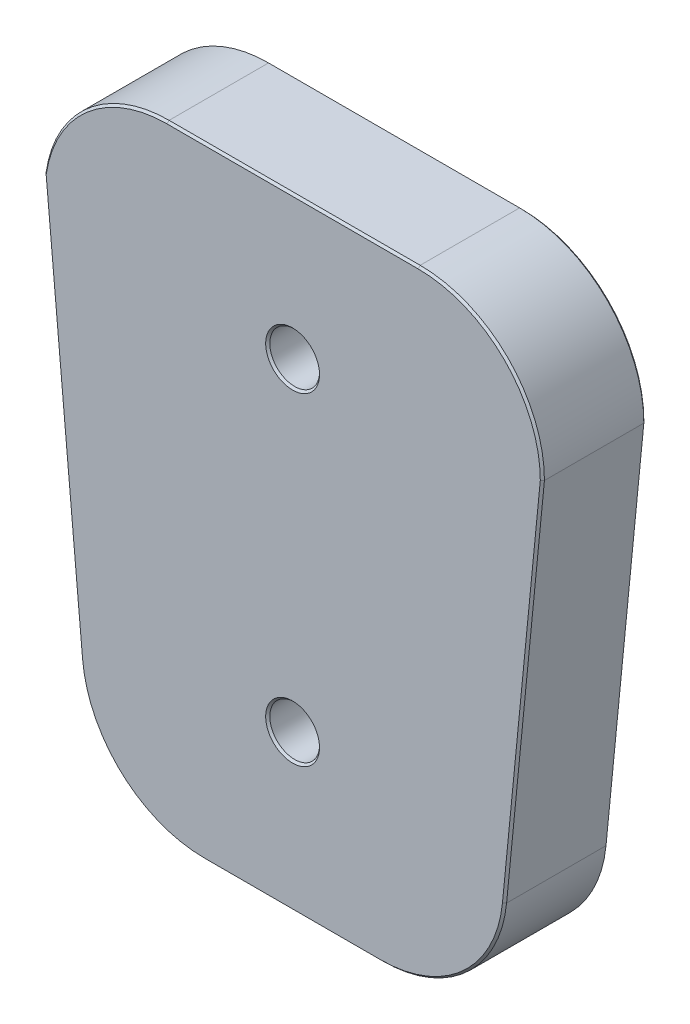
SolidWorks part; units mm, degrees
ref_plane "Front Plane" through (0, 0, 0) normal (0, 0, 1) x (1, 0, 0)
ref_plane "Top Plane" through (0, 0, 0) normal (0, 1, 0) x (1, 0, 0)
ref_plane "Right Plane" through (0, 0, 0) normal (1, 0, 0) x (0, 0, -1)
sketch "Sketch3" plane through (0, 0, 0) normal (0, 0, 1) x (1, 0, 0)
  line L0 (0, -25.6956) -> (8.8067, -122.7121)
  line L1 (29.6896, 0) -> (90.3104, 0)
  line L5 (38.6838, -150) -> (81.3162, -150)
  line L6 (111.1722, -122.9357) -> (120.3104, -30)
  line L7 (60, 0) -> (60, -173.3588) construction
  arc A0 (90.3104, 0) -> (120.3104, -30) centre (90.3104, -30) cw
  arc A1 (29.6896, 0) -> (0, -25.6956) centre (29.6896, -30) ccw
  arc A2 (81.3162, -150) -> (111.1722, -122.9357) centre (81.3162, -120) ccw
  arc A3 (8.8067, -122.7121) -> (38.6838, -150) centre (38.6838, -120) ccw
  point P7 (120, 0)
  point P10 (0, 0)
  point P13 (60, -150)
  dimension "D3" = 30
  dimension "D5" = 30
  dimension "D2" = 150
  dimension "D4" = 0
extrude "Boss-Extrude1" add sketch "Sketch3" along normal blind 25 contours A3 L5 A2 L6 A0 L1 A1 L0
sketch "Sketch4" plane through (0, 0, 25) normal (0, 0, 1) x (1, 0, 0)
  line L0 (60, 0) -> (60, -69) construction
  line L1 (29.6896, 0) -> (90.3104, 0) construction
  line L2 (38.6838, -150) -> (81.3162, -150) construction
  line L3 (60, 0) -> (60, -69) construction
  line L4 (60, -75) -> (60, -150) construction
  line L5 (60, -75) -> (60, -150) construction
  circle A1 centre (60, -34.5) radius 6
  circle A2 centre (60, -112.5) radius 6
  dimension "D1" = 12
  dimension "D3" = 12
extrude "Cut-Extrude1" cut sketch "Sketch4" against normal blind 12
sketch "Sketch5" plane through (0, 0, 13) normal (0, 0, 1) x (1, 0, 0)
  circle A0 centre (60, -34.5) radius 3.2
  circle A2 centre (60, -112.5) radius 3.2
  dimension "D1" = 6.4
  dimension "D3" = 6.4
extrude "Cut-Extrude2" cut sketch "Sketch5" against normal through all
chamfer "Chamfer1" distance 0.5 angle 45 20 edges at (18.4522, -142.1513, 0) (60, -150, 0) (101.4647, -142.2269, 0) (115.7413, -76.4678, 0) (111.5236, -8.7868, 0) (60, 0, 0) (10.0571, -7.3159, 0) (4.4033, -74.2038, 0) (63.2, -112.5, 0) (63.2, -34.5, 0) (10.0571, -7.3159, 25) (60, 0, 25) (111.5236, -8.7868, 25) (115.7413, -76.4678, 25) (101.4647, -142.2269, 25) (60, -150, 25) (18.4522, -142.1513, 25) (4.4033, -74.2038, 25) (66, -34.5, 25) (66, -112.5, 25)
equation "\"D3@Sketch4\"= \"D1@Sketch4\""
equation "\"D3@Sketch5\"=\"D1@Sketch5\""
